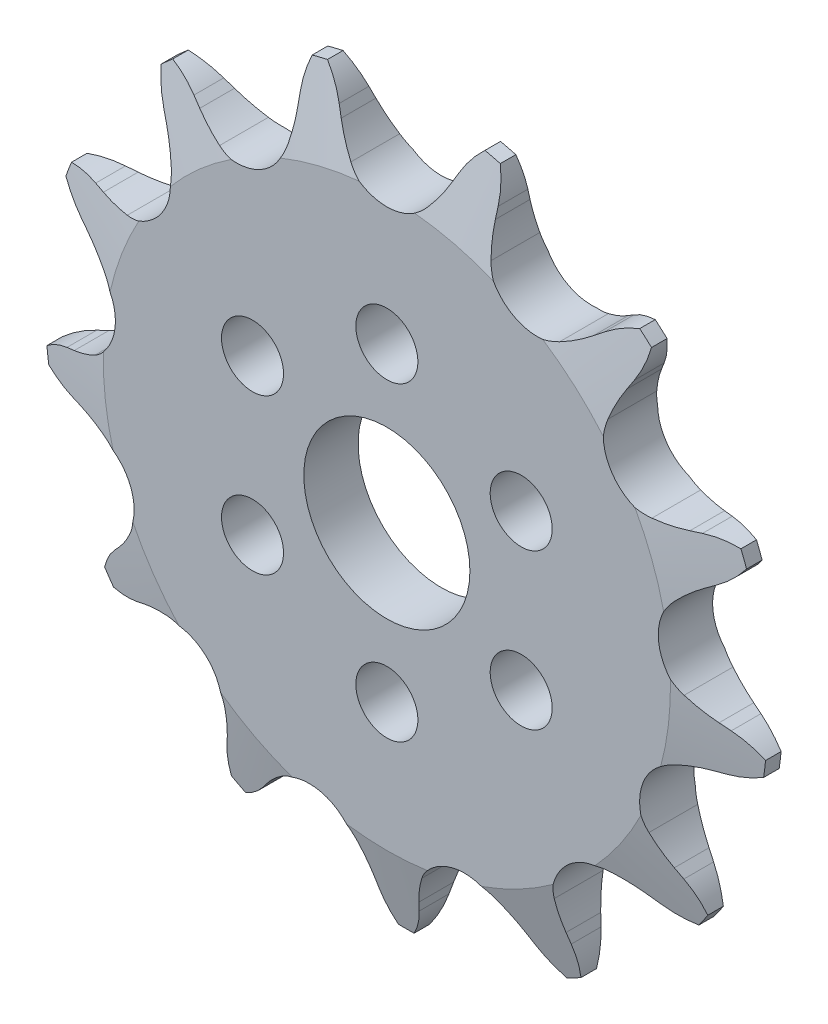
SolidWorks part; units mm, degrees
material "AISI 4130 Steel, annealed at 865C"
ref_plane "Front Plane" through (0, 0, 0) normal (0, 0, 1) x (1, 0, 0)
ref_plane "Top Plane" through (0, 0, 0) normal (0, 1, 0) x (1, 0, 0)
ref_plane "Right Plane" through (0, 0, 0) normal (1, 0, 0) x (0, 0, -1)
sketch "Sketch0" plane through (0, 0, 0) normal (0, 0, 1) x (1, 0, 0)
  line L0 (7.9375, -32.2037) -> (0, 0) construction
  line L1 (0, 0) -> (21.9941, -24.8262) construction
  line L2 (0, 0) -> (-7.9375, -32.2037) construction
  line L3 (7.9375, -32.2037) -> (21.9941, -24.8262) construction
  line L4 (7.9375, -32.2037) -> (-7.9375, -32.2037) construction
  line L5 (13.9722, -31.0531) -> (13.2992, -30.2445)
  line L6 (7.9375, -32.2037) -> (0, -34.1601) construction
  line L7 (2.0593, -33.9894) -> (2.2794, -32.9606)
  line L8 (0, -32.2037) -> (0, -36.9662) construction
  line L9 (10.9997, -28.0711) -> (3.0984, -38.7342) construction
  line L10 (0, 0) -> (0, -32.2037) construction
  line L11 (13.2992, -30.2445) -> (3.0984, -38.7342) construction
  line L12 (0, -36.9662) -> (0, -37.9761) construction
  line L13 (20.5322, -25.5935) -> (13.9722, -31.0531) construction
  circle A0 centre (0, 0) radius 36.9662 construction
  circle A1 centre (0, 0) radius 33.1675 construction
  arc A2 (-7.9217, -40.5803) -> (25.8729, -32.2507) centre (0, 0) ccw
  circle A3 centre (0, 0) radius 37.9761 construction
  circle A4 centre (7.9375, -32.2037) radius 5.08 construction
  arc A7 (10.9997, -28.0711) -> (3.3055, -29.9676) centre (7.9375, -32.2037) ccw
  circle A8 centre (7.9375, -32.2037) radius 5.1435 construction
  arc A9 (13.9722, -31.0531) -> (25.8729, -32.2507) centre (20.5322, -25.5935) ccw
  arc A10 (13.2992, -30.2445) -> (10.9997, -28.0711) centre (3.0984, -38.7342) ccw
  arc A11 (2.0593, -33.9894) -> (-7.9217, -40.5803) centre (-6.2865, -32.2037) cw
  arc A12 (2.2794, -32.9606) -> (3.3055, -29.9676) centre (15.2572, -35.7373) cw
  dimension "D1" = 5.1435
  dimension "R" = 5.1435
sketch "Sketch1" plane through (0, 0, 0) normal (1, 0, 0) x (0, 0, -1)
  line L0 (2.7781, 0) -> (-2.7781, 0)
  line L1 (-2.7781, 0) -> (-2.7781, 29.0287)
  line L2 (-2.7781, 29.0287) -> (-0.7937, 36.9662)
  line L3 (-0.7937, 36.9662) -> (0.7937, 36.9662)
  line L4 (0.7937, 36.9662) -> (2.7781, 29.0287)
  line L5 (2.7781, 29.0287) -> (2.7781, 0)
  line L7 (0, 36.9662) -> (0, 0) construction
  line L8 (-2.7781, 29.0287) -> (2.7781, 29.0287) construction
  line L9 (0, 36.9662) -> (0, -36.9662) construction
  line L10 (-2.7781, 29.0287) -> (-2.7781, 36.9662) construction
  line L11 (-2.7781, 36.9662) -> (-0.7937, 36.9662) construction
  line L12 (0.7937, 36.9662) -> (2.7781, 36.9662) construction
  line L13 (2.7781, 36.9662) -> (2.7781, 29.0287) construction
revolve "Revolve1" add sketch "Sketch1" angle 360 mid plane about L0
extrude "Cut-Extrude1" cut sketch "Sketch0" against normal through all and the other way through all
pattern_circular "CirPattern1" count 13 over 360 about axis through (0, 0, -2.7781) along (0, 0, -1) of "Cut-Extrude1"
sketch "Sketch2" plane through (0, 0, 0) normal (0, 0, 1) x (1, 0, 0)
  circle A0 centre (0, 0) radius 7.9375 construction
  circle A1 centre (0, 0) radius 30.1625
  circle A2 centre (0, 0) radius 36.957 construction
  dimension "Bore" = 15.875
  dimension "Hub Dia." = 60.325
  dimension "OD" = 73.914
sketch "Sketch3" plane through (0, 0, 0) normal (0, 0, 1) x (1, 0, 0)
  circle A1 centre (0, 0) radius 8.5
  circle A2 centre (0, 0) radius 36.957 construction
  circle A3 centre (0, 0) radius 36.957
  dimension "D1" = 17
extrude "Cut-Extrude2" cut sketch "Sketch3" along normal through all and the other way through all flip side to cut
sketch "Sketch4" plane through (0, 0, -2.7781) normal (0, 0, -1) x (-1, 0, 0)
  line L0 (0, 0) -> (0, 15.875) construction
  circle A0 centre (0, 15.875) radius 3.175
  circle A1 centre (13.7482, 7.9375) radius 3.175
  circle A2 centre (13.7482, -7.9375) radius 3.175
  circle A3 centre (0, -15.875) radius 3.175
  circle A4 centre (-13.7482, -7.9375) radius 3.175
  circle A5 centre (-13.7482, 7.9375) radius 3.175
  point P17 (0, 0)
  dimension "D1" = 6
extrude "Cut-Extrude3" cut sketch "Sketch4" against normal through all
sketch "Sketch5" plane through (0, 0, 2.7781) normal (0, 0, 1) x (1, 0, 0)
  line L0 (0, 0) -> (8.5, 0) construction
  line L1 (8.5, 0) -> (11, 0) construction
  circle A0 centre (0, 0) radius 11 construction
  circle A1 centre (0, 0) radius 8.5 construction
sketch "Sketch6" plane through (0, 0, -2.7781) normal (0, 0, -1) x (-1, 0, 0)
  circle A0 centre (0, 0) radius 28.024 construction
  circle A1 centre (0, 0) radius 24.2521 construction
ref_plane "Plane1" through (-29.6833, 20.4889, 0) normal (-0.823, 0.5681, 0) x (0, 0, 1)
ref_plane "Plane2" through (-35.8049, 4.3475, 0) normal (-0.9927, 0.1205, 0) x (0, 0, 1)
ref_plane "Plane3" through (-33.724, -12.7898, 0) normal (-0.935, -0.3546, 0) x (0, 0, 1)
ref_plane "Plane4" through (-23.9174, -26.9972, 0) normal (-0.6631, -0.7485, 0) x (-0.7485, 0.6631, 0)
ref_plane "Plane5" through (-8.6316, -35.0198, 0) normal (-0.2393, -0.9709, 0) x (-0.9709, 0.2393, 0)
sketch "Sketch7" plane through (-29.6833, 20.4889, 0) normal (-0.823, 0.5681, 0) x (0, 0, 1)
  line L0 (-6.5106, 0) -> (7.7601, 0)
sketch "Sketch8" plane through (-35.8049, 4.3475, 0) normal (-0.9927, 0.1205, 0) x (0, 0, 1)
  line L0 (-7.786, 0) -> (10.2102, 0)
sketch "Sketch9" plane through (-33.724, -12.7898, 0) normal (-0.935, -0.3546, 0) x (0, 0, 1)
  line L0 (-7.6671, 0) -> (14.0341, 0)
  line L1 (-2.7781, 0) -> (2.7781, 0) construction
sketch "Sketch10" plane through (-23.9174, -26.9972, 0) normal (-0.6631, -0.7485, 0) x (-0.7485, 0.6631, 0)
  line L0 (0, -3.5829) -> (0, 5.4944)
sketch "Sketch11" plane through (-8.6316, -35.0198, 0) normal (-0.2393, -0.9709, 0) x (-0.9709, 0.2393, 0)
  line L0 (0, -5.4358) -> (0, 8.5188)
split line "Split Line7"
split line "Split Line8"
split line "Split Line9"
split line "Split Line10"
split line "Split Line11"
ref_plane "Motor Sprocket Middle Plane" through (0, 0, -0.0019) normal (0, 0, 1) x (1, 0, 0)
equation "\"360/N@Sketch0\" = 360/\"Teeth@CirPattern1\""
equation "\"Ds@Sketch0\" = 1.005 * \"Dr@Sketch0\" + 0.003"
equation "\"R@Sketch0\" = 1/2 * \"Ds@Sketch0\""
equation "\"A@Sketch0\" = 35 +  ( 60 / \"Teeth@CirPattern1\" ) "
equation "\"B@Sketch0\" = 18 -  ( 56 / \"Teeth@CirPattern1\" )"
equation "\"ac@Sketch0\" = 0.8 * \"Dr@Sketch0\""
equation "\"ab@Sketch0\" = 1.4 * \"Dr@Sketch0\""
equation "\"J@Sketch0\" = 0.3 * \"Pitch@Sketch0\""
equation "\"h@Sketch1\" = \"Pitch@Sketch0\" / 2"
equation "\"g@Sketch1\" = \"h@Sketch1\" / 4"
